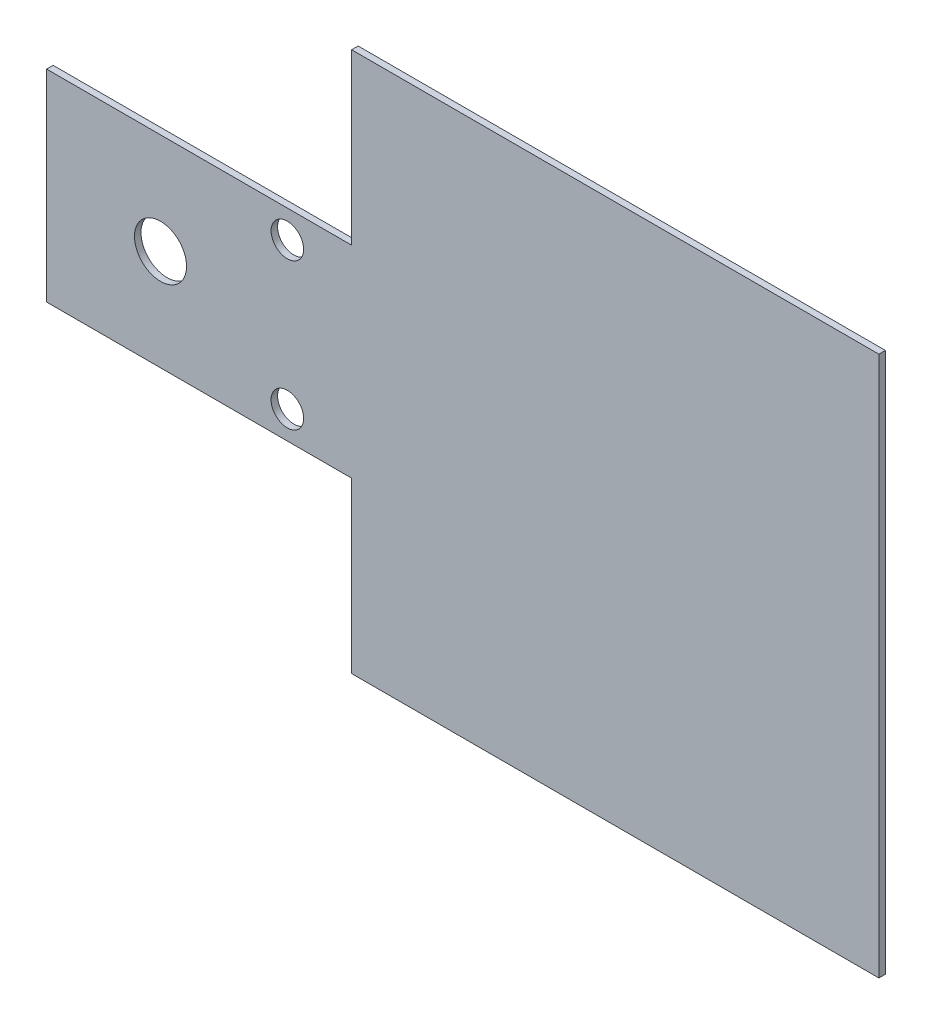
SolidWorks part; units mm, degrees
material "201 Annealed Stainless Steel (SS)"
ref_plane "Front Plane" through (0, 0, 0) normal (0, 0, 1) x (1, 0, 0)
ref_plane "Top Plane" through (0, 0, 0) normal (0, 1, 0) x (1, 0, 0)
ref_plane "Right Plane" through (0, 0, 0) normal (1, 0, 0) x (0, 0, -1)
sketch "Sketch1" plane through (0, 0, 0) normal (0, 0, 1) x (1, 0, 0)
  line L1 (-81, -120) -> (81, -120)
  line L2 (-81, -120) -> (-81, 120)
  line L3 (-81, 120) -> (81, 120)
  line L4 (81, -120) -> (81, 120)
  line L5 (-81, -120) -> (81, 120) construction
  line L6 (-81, 120) -> (81, -120) construction
  point P0 (0, 0)
  dimension "D1" = 162
  dimension "D2" = 240
extrude "Boss-Extrude1" add sketch "Sketch1" along normal blind 2
sketch "Sketch2" [suppressed] plane through (0, 0, 0) normal (0, 0, -1) x (-1, 0, 0)
  line L0 (61, 200) -> (61, -200) construction
  line L1 (-61, 314.7216) -> (-204.3993, 314.7216)
  line L2 (-61, 314.7216) -> (-61, -251.9618)
  line L3 (-61, -251.9618) -> (-204.3993, -251.9618)
  line L4 (-204.3993, 314.7216) -> (-204.3993, -251.9618)
  line L6 (61, 279.3211) -> (244.4765, 279.3211)
  line L7 (61, 279.3211) -> (61, -295.1839)
  line L8 (61, -295.1839) -> (244.4765, -295.1839)
  line L9 (244.4765, 279.3211) -> (244.4765, -295.1839)
  line L10 (-61, -200) -> (-61, -140) construction
  dimension "D1" = 122
extrude "Cut-Extrude1" [suppressed] cut sketch "Sketch2" against normal through all
sketch "Sketch3" [suppressed] plane through (75, 0, 0) normal (1, 0, 0) x (0, 0, -1)
  line L0 (-2, 90) -> (0, 90) construction
  line L1 (-2, 90) -> (-2, -90) construction
  circle A0 centre (-7, 75) radius 2.5
  dimension "D3" = 5
  dimension "D1" = 15
  dimension "D2" = 5
surface "Surface-Extrude1" [suppressed] sketch "Sketch3"
sketch "Sketch4" plane through (-81, 0, 0) normal (-1, 0, 0) x (0, 0, 1)
  line L1 (2, 120) -> (0, 120) construction
  line L2 (0, -120) -> (0, 120) construction
  point P0 (7.5, 116)
  dimension "D1" = 4
  dimension "D2" = 7.5
ref_axis "Axis1" through (-81, 116, 7.5) along (1, 0, 0)
sketch "Sketch5" [suppressed] plane through (0, 0, 0) normal (0, 0, -1) x (-1, 0, 0)
  line L0 (49, 80) -> (49, -80) construction
  line L1 (-49, 80) -> (49, 80)
  line L2 (-49, 80) -> (-49, 60.2594)
  line L3 (-49, 60.2594) -> (49, 60.2594)
  line L4 (49, 80) -> (49, 60.2594)
extrude "Cut-Extrude2" [suppressed] cut sketch "Sketch5" against normal blind 3
sketch "Sketch6" [suppressed] plane through (0, 0, 2) normal (0, 0, 1) x (1, 0, 0)
  line L0 (0, 0) -> (103.2002, 0) construction
  line L1 (-40, 80) -> (-40, 108.3319) construction
  line L2 (-40, 80) -> (-27.987, 80) construction
  line L3 (0, 0) -> (0, 138.3235) construction
  line L4 (40, 80) -> (27.987, 80) construction
  line L5 (40, 80) -> (40, 108.3319) construction
  line L6 (40, -80) -> (40, -108.3319) construction
  line L7 (40, -80) -> (27.987, -80) construction
  line L8 (-40, -80) -> (-27.987, -80) construction
  line L9 (-40, -80) -> (-40, -108.3319) construction
  circle A0 centre (-40, 80) radius 4.5
  circle A2 centre (-45.8, 85.8) radius 1.95
  circle A3 centre (-45.8, 74.2) radius 1.95
  circle A4 centre (-34.2, 74.2) radius 1.95
  circle A5 centre (-34.2, 85.8) radius 1.95
  circle A6 centre (34.2, 85.8) radius 1.95
  circle A7 centre (34.2, 74.2) radius 1.95
  circle A8 centre (45.8, 74.2) radius 1.95
  circle A9 centre (45.8, 85.8) radius 1.95
  circle A10 centre (40, 80) radius 4.5
  circle A11 centre (40, -80) radius 4.5
  circle A12 centre (45.8, -85.8) radius 1.95
  circle A13 centre (45.8, -74.2) radius 1.95
  circle A14 centre (34.2, -74.2) radius 1.95
  circle A15 centre (34.2, -85.8) radius 1.95
  circle A16 centre (-34.2, -85.8) radius 1.95
  circle A17 centre (-34.2, -74.2) radius 1.95
  circle A18 centre (-45.8, -74.2) radius 1.95
  circle A19 centre (-45.8, -85.8) radius 1.95
  circle A20 centre (-40, -80) radius 4.5
  circle A21 centre (-40, 80) radius 5.1 construction
  dimension "D1" = 9
  dimension "D3" = 3.9
extrude "Leandut_holes" [suppressed] cut sketch "Sketch6" against normal through all
chamfer "Chamfer1" [suppressed] distance 5 angle 45
sketch "Sketch7" plane through (0, 0, 2) normal (0, 0, 1) x (1, 0, 0)
  line L0 (81, 120) -> (-81, 120) construction
  line L1 (-31, -125) -> (31, -125)
  line L2 (-31, -125) -> (-31, 100)
  line L3 (-31, 100) -> (31, 100)
  line L4 (31, -125) -> (31, 100)
  line L5 (0, 0) -> (0, -66.8576) construction
  line L7 (-81, 120) -> (-81, -120) construction
  point P0 (0, 0)
  dimension "D1" = 20
  dimension "D2" = 50
  dimension "D3" = 62
  dimension "D4" = 125
extrude "Plunger-Window" [suppressed] cut sketch "Sketch7" against normal through all
sketch "Sketch8" [suppressed] plane through (0, 0, 2) normal (0, 0, 1) x (1, 0, 0)
  line L0 (106, 145) -> (56, 145) construction
  line L1 (-56, 125) -> (56, 125)
  line L2 (-56, 125) -> (-56, 145)
  line L3 (-56, 145) -> (56, 145)
  line L4 (56, 125) -> (56, 145)
  line L5 (56, -110) -> (56, 125) construction
extrude "Cut-Extrude3" [suppressed] cut sketch "Sketch8" against normal blind 5
sketch "Sketch9" plane through (0, 0, 0) normal (0, 0, -1) x (-1, 0, 0)
  line L0 (1.1, 0) -> (-1.1, 0) construction
  line L5 (6, -100) -> (-6, -100)
  line L6 (6, -100) -> (6, 100)
  line L7 (6, 100) -> (-6, 100)
  line L8 (-6, -100) -> (-6, 100)
  line L9 (-81, 120) -> (81, 120) construction
  point P0 (0, 0)
  point P8 (0, 100)
  dimension "D1" = 12
  dimension "D2" = 100
  dimension "D3" = 100
  dimension "D4" = 20
extrude "Plunger-cutout" [suppressed] cut sketch "Sketch9" against normal through all and the other way through all
sketch "Sketch10" plane through (0, 0, 0) normal (0, 0, -1) x (-1, 0, 0)
  line L0 (81, -147.5) -> (209.9137, 21.8916) construction
  line L1 (81, 120) -> (81, -120) construction
  line L2 (81, 120) -> (209.9137, 21.8916) construction
  line L3 (81, 120) -> (81, -147.5) construction
  line L4 (-81, 120) -> (81, 120) construction
  line L5 (-81, 120) -> (81, 120) construction
  line L6 (0, 120) -> (0, 262.0874) construction
  line L7 (-81, 120) -> (-81, -147.5)
  line L8 (-81, 120) -> (-209.9137, 21.8916)
  line L9 (-81, -147.5) -> (-209.9137, 21.8916)
  line L10 (81, 120) -> (81, -120) construction
  dimension "D1" = 147.5
  dimension "D2" = 162
  dimension "D3" = 162
  dimension "D4" = 212.8667
  dimension "D5" = 240
extrude "Boss-Extrude3" [suppressed] add sketch "Sketch10" against normal through all
sketch "Sketch11" [suppressed] plane through (0, 0, 2) normal (0, 0, 1) x (1, 0, 0)
  line L0 (81, 217.5) -> (81, -274.1687)
split line "Split Line1" [suppressed]
sketch "Sketch12" plane through (0, 0, 0) normal (0, 0, -1) x (-1, 0, 0)
  line L0 (81, 120) -> (81, -120) construction
  line L4 (106.722, 31) -> (106.722, -31)
  line L5 (174.722, 31) -> (106.722, 31)
  line L6 (174.722, -31) -> (174.722, 31)
  line L7 (106.722, -31) -> (174.722, -31)
  line L8 (81, 31) -> (81, -31)
  line L9 (174.722, 31) -> (81, 31)
  line L10 (174.722, -31) -> (174.722, 31)
  line L11 (81, -31) -> (174.722, -31)
  circle A0 centre (139.72, 0) radius 8
  circle A4 centre (100.7508, -22.5) radius 5 construction
  circle A5 centre (100.7508, 22.5) radius 5 construction
  circle A6 centre (100.7508, -22.5) radius 5
  circle A7 centre (100.7508, 22.5) radius 5
  point P12 (0, 0)
  dimension "D3" = 16
  dimension "D5" = 139.72
  dimension "D1" = 0
extrude "Boss-Extrude4" add sketch "Sketch12" against normal through all
sketch "Sketch13" plane through (0, 0, 0) normal (0, 0, -1) x (-1, 0, 0)
  line L0 (0, 0) -> (-166.9371, 0) construction
  line L1 (108.207, -83) -> (-114.7867, -83)
  line L2 (108.207, -83) -> (108.207, -160.524)
  line L3 (108.207, -160.524) -> (-114.7867, -160.524)
  line L4 (-114.7867, -83) -> (-114.7867, -160.524)
  line L5 (-103.1423, 83) -> (143.0141, 83)
  line L6 (-103.1423, 83) -> (-103.1423, 164.1211)
  line L7 (-103.1423, 164.1211) -> (143.0141, 164.1211)
  line L8 (143.0141, 83) -> (143.0141, 164.1211)
  dimension "D1" = 166
extrude "Cut-Extrude4" cut sketch "Sketch13" against normal through all
